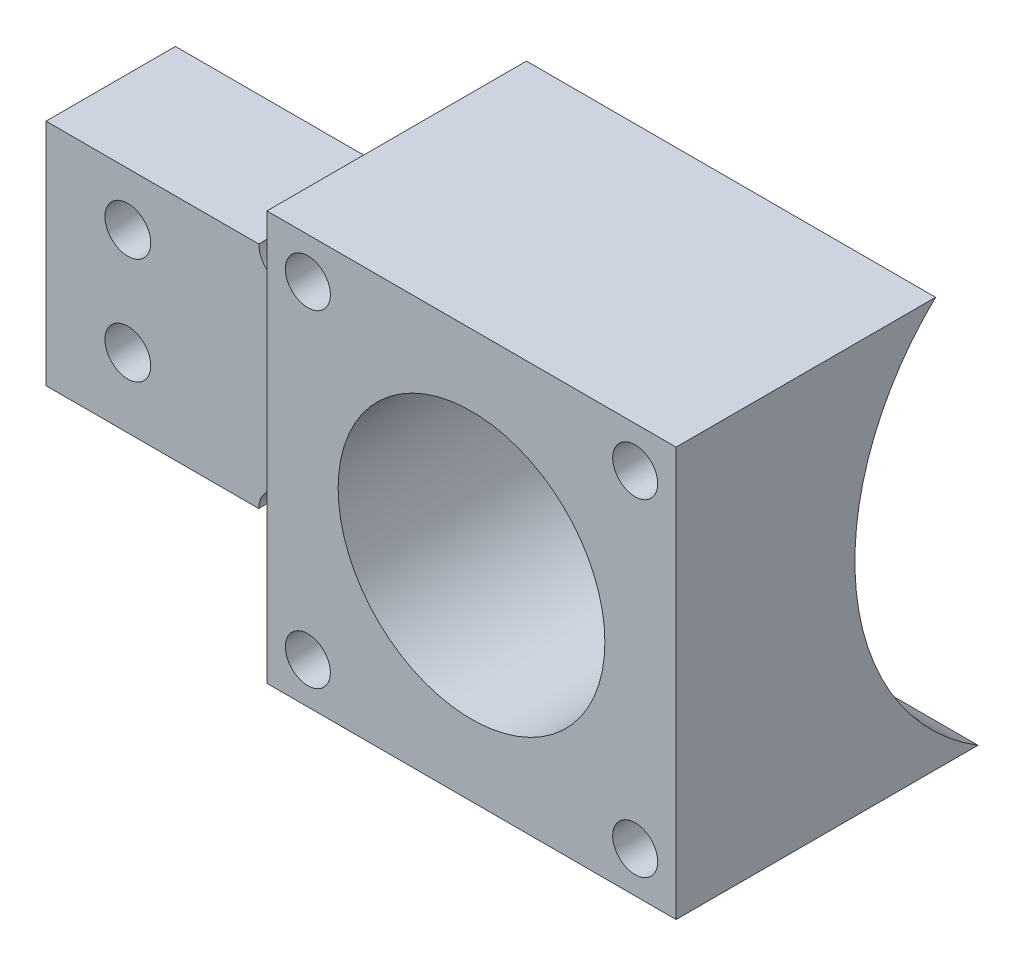
SolidWorks part; units mm, degrees
ref_plane "Front Plane" through (0, 0, 0) normal (0, 0, 1) x (1, 0, 0)
ref_plane "Top Plane" through (0, 0, 0) normal (0, 1, 0) x (1, 0, 0)
ref_plane "Right Plane" through (0, 0, 0) normal (1, 0, 0) x (0, 0, -1)
sketch "Sketch1" plane through (0, 0, 0) normal (0, 0, 1) x (1, 0, 0)
  line L1 (-25, 23) -> (25, 23)
  line L2 (-25, 23) -> (-25, -27)
  line L3 (-25, -27) -> (25, -27)
  line L4 (25, 23) -> (25, -27)
  line L5 (-25, 23) -> (25, -27) construction
  line L6 (-25, -27) -> (25, 23) construction
  circle A0 centre (0, -2) radius 16.3
  circle A1 centre (-20, 18) radius 2.75
  circle A2 centre (20, 18) radius 2.75
  circle A3 centre (20, -22) radius 2.75
  circle A4 centre (-20, -22) radius 2.75
  point P0 (0, -2)
  dimension "D4" = 32.6
  dimension "D6" = 5.5
  dimension "D1" = 2
  dimension "D2" = 50
  dimension "D3" = 50
  dimension "D5" = 20
  dimension "D7" = 20
  dimension "D9" = 20
  dimension "D10" = 20
extrude "Boss-Extrude1" add sketch "Sketch1" along normal blind 53.6
sketch "Sketch2" plane through (0, 0, 0) normal (1, 0, 0) x (0, 0, -1)
  circle A0 centre (0, 0) radius 31.75
  dimension "D1" = 63.5
extrude "Cut-Extrude1" cut sketch "Sketch2" against normal through all and the other way through all
sketch "Sketch3" plane through (-25, 0, 0) normal (-1, 0, 0) x (0, 0, 1)
  line L3 (53.6, 23) -> (21.8875, 23)
  line L4 (16.7052, -27) -> (53.6, -27)
  line L5 (53.6, -27) -> (53.6, 23)
  line L6 (53.6, 23) -> (21.8875, 23)
  line L7 (16.7052, -27) -> (53.6, -27)
  line L8 (53.6, -27) -> (53.6, 23)
  arc A1 (16.7052, -27) -> (21.8875, 23) centre (0, 0) ccw
  arc A2 (16.7052, -27) -> (21.8875, 23) centre (0, 0) ccw
  dimension "D1" = 0
sketch "Sketch4" plane through (25, 0, 0) normal (1, 0, 0) x (0, 0, -1)
  line L3 (-53.6, -27) -> (-16.7052, -27)
  line L4 (-21.8875, 23) -> (-53.6, 23)
  line L5 (-53.6, 23) -> (-53.6, -27)
  line L8 (-53.6, 11) -> (-53.6, -17)
  line L12 (-53.6, 11) -> (-29.7836, 11)
  line L13 (-53.6, 23) -> (-21.8875, 23) construction
  line L14 (0, 0) -> (-85.4701, 0) construction
  line L15 (-53.6, -11) -> (-29.7836, -11) construction
  line L16 (-53.6, -17) -> (-26.8153, -17)
  arc A0 (-21.8875, 23) -> (-16.7052, -27) centre (0, 0) ccw construction
  arc A1 (-21.8875, 23) -> (-16.7052, -27) centre (0, 0) ccw
  arc A2 (-29.7836, 11) -> (-26.8153, -17) centre (0, 0) ccw
  dimension "D3" = 12
  dimension "D4" = 6
  dimension "D1" = 0
extrude "Boss-Extrude3" add sketch "Sketch4" along normal blind 35
sketch "Sketch12" plane through (0, 0, 53.6) normal (0, 0, 1) x (1, 0, 0)
  line L6 (60, 11) -> (60, -17) construction
  line L7 (60, 11) -> (25, 11) construction
  line L8 (60, -17) -> (25, -17) construction
  line L9 (60, 11) -> (60, -17)
  line L10 (60, 11) -> (25, 11)
  line L11 (60, -17) -> (25, -17)
  line L12 (25, 11) -> (25, -17)
extrude "Cut-Extrude7" cut sketch "Sketch12" against normal blind 8
sketch "Sketch9" plane through (0, 0, 0) normal (0, 0, 1) x (1, 0, 0)
  line L0 (31, 11) -> (31, -17) construction
  line L1 (60, 11) -> (25, 11) construction
  line L2 (25, -17) -> (60, -17) construction
  line L3 (25, -27) -> (25, 23) construction
  circle A4 centre (31, 11) radius 3
  circle A5 centre (31, -17) radius 3
  point P6 (0, 0)
  point P9 (0, 0)
  dimension "D1" = 6
  dimension "D2" = 6
extrude "Cut-Extrude5" cut sketch "Sketch9" against normal through all both and the other way through all
sketch "Sketch10" plane through (0, 0, 45.6) normal (0, 0, 1) x (1, 0, 0)
  line L0 (50, 4.5) -> (50, -8.5) construction
  line L1 (60, -2) -> (0, -2) construction
  line L3 (25, -27) -> (25, 23) construction
  line L5 (50, 22) -> (50, -27) construction
  line L6 (-25, -27) -> (25, -27) construction
  line L7 (60, 11) -> (60, -17) construction
  circle A0 centre (50, 4.5) radius 2.8
  circle A1 centre (50, -8.5) radius 2.8
  point P8 (50, -2)
  point P19 (60, -3)
  dimension "D1" = 5.6
  dimension "D2" = 1
  dimension "D3" = 13
  dimension "D4" = 25
extrude "Cut-Extrude6" cut sketch "Sketch10" against normal blind 10 and the other way through all
ref_plane "Plane1" through (0, 0, 0) normal (1, 0, 0) x (0, 0, -1)
mirror "Mirror3" about plane through (0, 0, 0) normal (1, 0, 0) of "Cut-Extrude6", "Cut-Extrude5", "Cut-Extrude7", "Boss-Extrude3"
sketch "Sketch13" plane through (0, 0, 45.6) normal (0, 0, 1) x (1, 0, 0)
  line L0 (28, 11) -> (25, 11) construction
  line L1 (60, 11) -> (34, 11) construction
  line L2 (60, -17) -> (60, 11) construction
  line L3 (34, -17) -> (60, -17) construction
  line L4 (25, -17) -> (28, -17) construction
  line L5 (25, 11) -> (25, -17) construction
  line L6 (25, 11) -> (25, -17)
  line L7 (25, -17) -> (28, -17)
  line L8 (34, -17) -> (60, -17)
  line L9 (60, -17) -> (60, 11)
  line L10 (60, 11) -> (34, 11)
  line L11 (28, 11) -> (25, 11)
  arc A0 (28, 11) -> (34, 11) centre (31, 11) ccw construction
  arc A1 (34, -17) -> (28, -17) centre (31, -17) ccw construction
  arc A2 (34, -17) -> (28, -17) centre (31, -17) ccw
  arc A3 (28, 11) -> (34, 11) centre (31, 11) ccw
extrude "Cut-Extrude8" cut sketch "Sketch13" against normal through all
